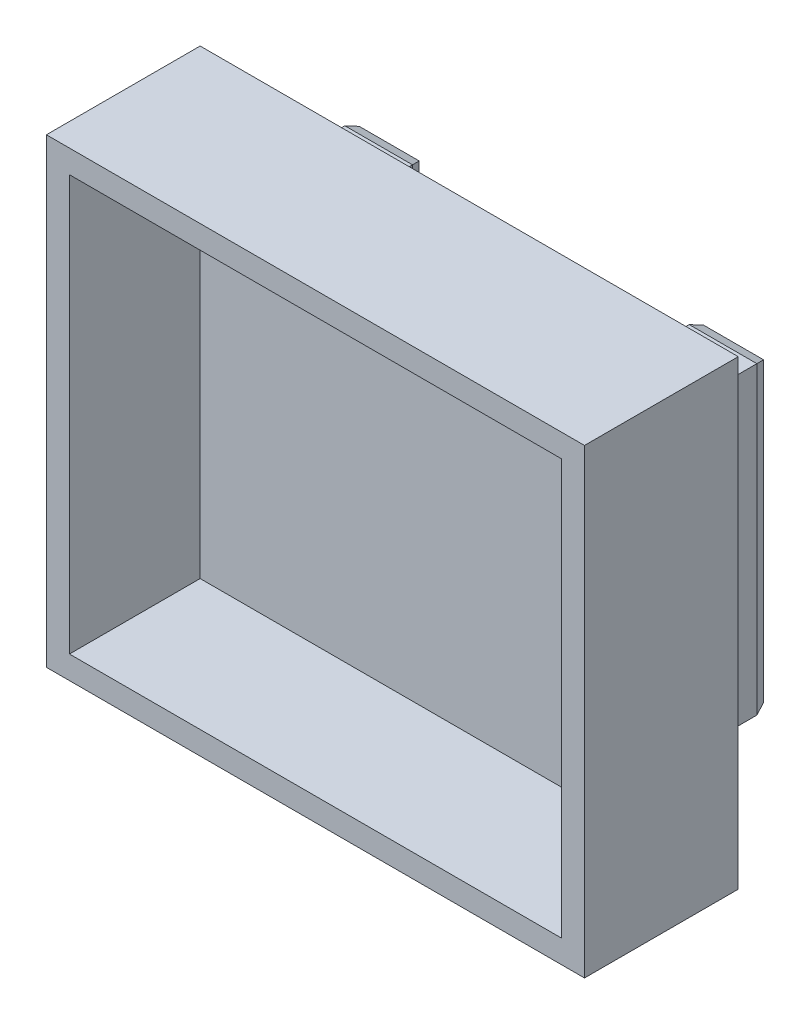
SolidWorks part; units mm, degrees
ref_plane "Спереди" through (0, 0, 0) normal (0, 0, 1) x (1, 0, 0)
ref_plane "Сверху" through (0, 0, 0) normal (0, 1, 0) x (1, 0, 0)
ref_plane "Справа" through (0, 0, 0) normal (1, 0, 0) x (0, 0, -1)
sketch "Sketch2" plane through (0, 0, 0) normal (0, 0, 1) x (1, 0, 0)
  line L1 (26.8, -19.8) -> (-26.8, -19.8)
  line L2 (26.8, -19.8) -> (26.8, 19.8)
  line L3 (26.8, 19.8) -> (-26.8, 19.8)
  line L4 (-26.8, -19.8) -> (-26.8, 19.8)
  line L5 (26.8, -19.8) -> (-26.8, 19.8) construction
  line L6 (26.8, 19.8) -> (-26.8, -19.8) construction
  point P0 (0, 0)
  dimension "D1" = 53.6
  dimension "D2" = 39.6
extrude "Boss-Extrude1" add sketch "Sketch2" along normal blind 12
sketch "Sketch3" plane through (0, 0, 12) normal (0, 0, 1) x (1, 0, 0)
  line L0 (0, 19.8) -> (0, -19.8) construction
  line L1 (35, -30) -> (-35, -30)
  line L2 (35, -30) -> (35, 30)
  line L3 (35, 30) -> (-35, 30)
  line L4 (-35, -30) -> (-35, 30)
  line L5 (35, -30) -> (-35, 30) construction
  line L6 (35, 30) -> (-35, -30) construction
  line L7 (26.8, 19.8) -> (-26.8, 19.8) construction
  line L8 (-26.8, -19.8) -> (26.8, -19.8) construction
  point P0 (0, 0)
  point P6 (0, 4.8706)
  point P7 (0, 0)
  dimension "D1" = 70
  dimension "D2" = 60
  dimension "D3" = 0
extrude "Boss-Extrude2" add sketch "Sketch3" along normal blind 20
sketch "Sketch4" plane through (0, 19.8, 0) normal (0, 1, 0) x (1, 0, 0)
  line L0 (26.8, -4.6) -> (-26.8, -4.6) construction
  line L1 (26.8, -12) -> (26.8, 0) construction
  line L2 (-26.8, -12) -> (-26.8, 0) construction
  line L3 (26.8, -12) -> (-26.8, -12) construction
  circle A0 centre (22.5, -4.6) radius 2.1
  circle A1 centre (-22.5, -4.6) radius 2.1
  point P12 (0, -4.6)
  dimension "D2" = 4.2
  dimension "D3" = 4.2
  dimension "D1" = 7.4
  dimension "D4" = 45
  dimension "D5" = 22.5
extrude "Cut-Extrude1" cut sketch "Sketch4" against normal through all
sketch "Sketch5" plane through (0, 0, 0) normal (0, 0, -1) x (-1, 0, 0)
  line L0 (-26.8, 19.8) -> (26.8, 19.8) construction
  line L1 (18, -19.8) -> (-18, -19.8)
  line L2 (18, -19.8) -> (18, 19.8)
  line L3 (18, 19.8) -> (-18, 19.8)
  line L4 (-18, -19.8) -> (-18, 19.8)
  line L5 (18, -19.8) -> (-18, 19.8) construction
  line L6 (18, 19.8) -> (-18, -19.8) construction
  point P0 (0, 0)
  dimension "D1" = 36
extrude "Cut-Extrude2" cut sketch "Sketch5" against normal up to surface (12 mm away) up to face at (0, 0, 12)
chamfer "Chamfer1" distance 0.5 angle 70 8 edges at (26.8, 0, 0) (22.4, 19.8, 0) (18, 0, 0) (22.4, -19.8, 0) (-26.8, 0, 0) (-22.4, -19.8, 0) (-18, 0, 0) (-22.4, 19.8, 0) first distance on face at (22.4, 0, 0) first distance on face at (-22.4, 0, 0)
sketch "Sketch12" plane through (0, 0, 32) normal (0, 0, 1) x (1, 0, 0)
  line L0 (35, 30) -> (-35, 30) construction
  line L1 (32, -27) -> (-32, -27)
  line L2 (32, -27) -> (32, 27)
  line L3 (32, 27) -> (-32, 27)
  line L4 (-32, -27) -> (-32, 27)
  line L5 (32, -27) -> (-32, 27) construction
  line L6 (32, 27) -> (-32, -27) construction
  line L7 (-35, 30) -> (-35, -30) construction
  line L8 (0, -30) -> (0, 30) construction
  line L9 (-35, -30) -> (35, -30) construction
  line L10 (35, -30) -> (35, 30) construction
  point P0 (0, 0)
  point P10 (11.4549, 11.6802)
  dimension "D1" = 3
  dimension "D2" = 3
  dimension "D3" = 3
  dimension "D4" = 3
extrude "Cut-Extrude4" cut sketch "Sketch12" against normal offset from surface (17 mm away) 3 up to face at (-22.4, 0, 12)
